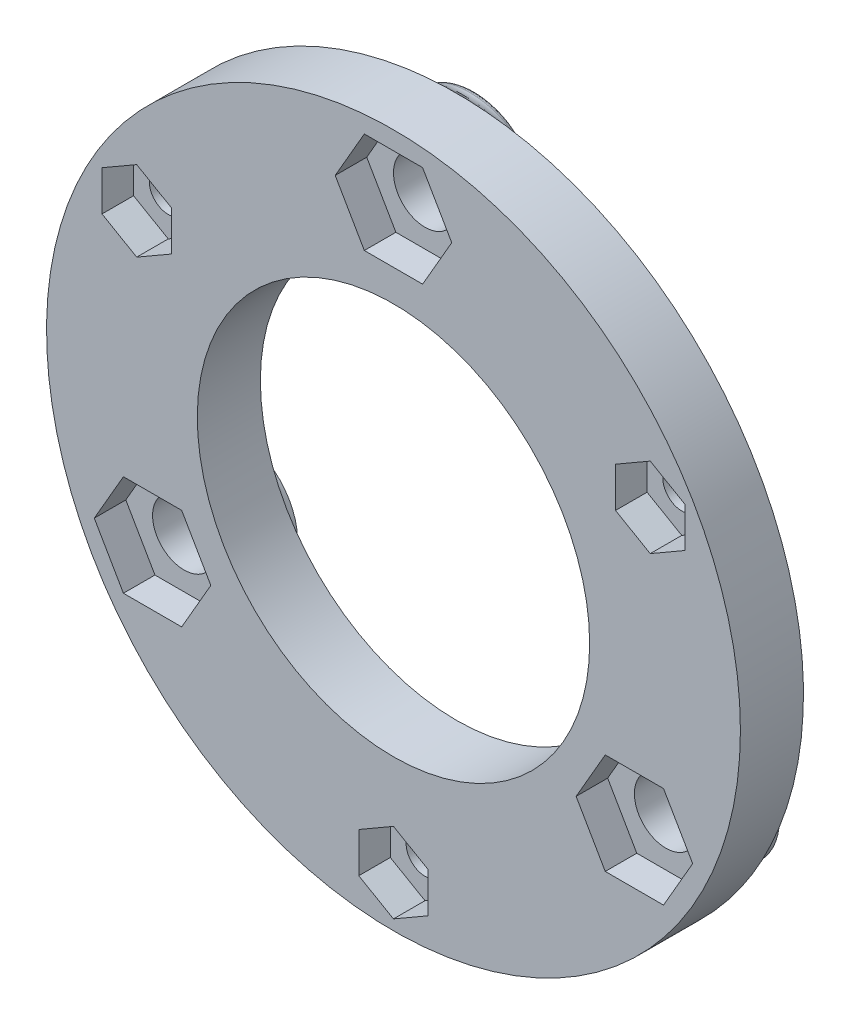
SolidWorks part; units mm, degrees
material "ABS"
ref_plane "Front Plane" through (0, 0, 0) normal (0, 0, 1) x (1, 0, 0)
ref_plane "Top Plane" through (0, 0, 0) normal (0, 1, 0) x (1, 0, 0)
ref_plane "Right Plane" through (0, 0, 0) normal (1, 0, 0) x (0, 0, -1)
sketch "Sketch2" plane through (0, 0, 0) normal (0, 0, 1) x (1, 0, 0)
  line L0 (0, 22.05) -> (0, 0) construction
  line L1 (0, 0) -> (20.3516, 11.75) construction
  circle A0 centre (0, 0) radius 27.5
  circle A1 centre (0, 0) radius 15.55
  circle A2 centre (0, 0) radius 22.05 construction
  circle A3 centre (0, 22.05) radius 2.5
  circle A4 centre (0, 0) radius 23.5 construction
  circle A5 centre (19.0959, -11.025) radius 2.5
  circle A8 centre (20.3516, 11.75) radius 1.5
  circle A9 centre (0, -23.5) radius 1.5
  circle A11 centre (0, 0) radius 6.3 construction
  circle A14 centre (0, 22.05) radius 5 construction
  circle A15 centre (0, 0) radius 17.05 construction
  circle A16 centre (-19.0959, -11.025) radius 2.5
  circle A19 centre (-20.3516, 11.75) radius 1.5
  point P17 (0, 0)
  point P24 (0, 0)
  dimension "D1" = 55
  dimension "D2" = 44.1
  dimension "D4" = 5
  dimension "D7" = 3
  dimension "D3" = 12.6
  dimension "D10" = 10
  dimension "D5" = 4
  dimension "D9" = 1.5
  dimension "D11" = 60
  dimension "D6" = 3
  dimension "D8" = 3
extrude "Boss-Extrude1" add sketch "Sketch2" along normal blind 5
sketch "Sketch3" plane through (0, 0, 5) normal (0, 0, 1) x (1, 0, 0)
  line L0 (0, 22.05) -> (0, 0) construction
  line L13 (-4.6188, 22.05) -> (-2.3094, 18.05)
  line L14 (-2.3094, 18.05) -> (2.3094, 18.05)
  line L15 (2.3094, 18.05) -> (4.6188, 22.05)
  line L16 (4.6188, 22.05) -> (2.3094, 26.05)
  line L17 (2.3094, 26.05) -> (-2.3094, 26.05)
  line L18 (-2.3094, 26.05) -> (-4.6188, 22.05)
  line L20 (20.3516, 8.5746) -> (23.1016, 10.1623)
  line L21 (23.1016, 10.1623) -> (23.1016, 13.3377)
  line L22 (23.1016, 13.3377) -> (20.3516, 14.9254)
  line L23 (20.3516, 14.9254) -> (17.6016, 13.3377)
  line L24 (17.6016, 13.3377) -> (17.6016, 10.1623)
  line L25 (17.6016, 10.1623) -> (20.3516, 8.5746)
  circle A0 centre (0, 22.05) radius 4 construction
  circle A1 centre (20.3516, 11.75) radius 2.75 construction
  dimension "D1" = 8
  dimension "D2" = 5.5
extrude "Cut-Extrude1" cut sketch "Sketch3" against normal blind 2.5
pattern_circular "CirPattern1" count 3 over 360 about axis through (0, 0, 5) along (0, 0, -1) of "Cut-Extrude1" reverse direction yes
sketch "Sketch4" plane through (0, 0, 0) normal (0, 0, -1) x (-1, 0, 0)
  circle A0 centre (0, 22.05) radius 4
  circle A1 centre (0, 22.05) radius 5
  dimension "D1" = 8
extrude "Boss-Extrude2" add sketch "Sketch4" along normal blind 1.5
fillet "Fillet1" radius 1.5 1 edges at (5, 22.05, 0)
fillet "Fillet2" radius 0.5 2 edges at (0, 27.05, -1.5) (0, 17.05, -1.5)
chamfer "Chamfer1" distance 0.25 angle 45 1 edges at (-4, 22.05, -1.5)
pattern_circular "CirPattern2" count 3 over 360 about axis through (0, 0, 5) along (0, 0, -1) of "Fillet1", "Boss-Extrude2", "Chamfer1" reverse direction yes
equation "\"Nr\"= 108"
equation "\"module\"= 0.7"
equation "\"pressure_angle\"= 20.0deg"
equation "\"h_a\"= 0.7"
equation "\"h_f\"= 0.875"
equation "\"clr_tip_root\"= 0.17500000000000004"
equation "\"dp_r\"= 75.6"
equation "\"db_r\"= 71.04076213141467"
equation "\"fw_r\"= 8.0"
equation "\"alpha_r\"= 0.8539582918412449"
equation "\"beta_r\"= 3.374583250349157"
equation "\"bearing_ID\"= 55"
equation "\"bearing_OD\"= 72"
equation "\"bearing_height\"= 9"
equation "\"clearance_planet\"= 1.5"
equation "\"case_dist\"= 6.5"
equation "\"Motor_case_OD_max\"= 111.3"
equation "\"case_mounting_PCD\"= 103.8"
equation "\"bearing mount thickness\"= 8"
equation "\"case_mounting_hole_dia\"= 3"
equation "\"output_mounting_PCD\"= 80"
equation "\"output_mounting_hole_dia\"= 4"
equation "\"clearance_case_mount_holes_shell_thickness\"= 1"
equation "\"motor_case_OD_base\"= 101.8"
equation "\"sec_carrier_thickness\"= 5"
equation "\"sun_coupler_hub_thickness\"= 4"
equation "\"clearance_sun_coupler_sec_carrier\"= 1.5"
equation "\"clearance_motor_and_case\"= 5"
equation "\"motor_OD\"= 86.8"
equation "\"Motor_case_thickness\"= 2.5"
equation "\"Motor_case_ID\"= 96.8"
equation "\"case_mounting_hole_shift\"= 1.0"
equation "\"output_mounting_nut_wrench_size\"= 7"
equation "\"output_mounting_nut_thickness\"= 3.2"
equation "\"case_mounting_hole_allen_socket_dia\"= 5.5"
equation "\"output_mounting_nut_depth\"= 3"
equation "\"case_mounting_bolt_depth\"= 4.5"
equation "\"Ns\"= 18"
equation "\"Np\"= 45"
equation "\"ring_radial_thickness\"= 5.0"
equation "\"ring_OD\"= 85.6"
equation "\"ring_to_chamfer_clearance\"= 2"
equation "\"Motor_case_OD_base_to_chamfer\"= 5"
equation "\"pattern_offset_from_motor_case_OD_base\"= 3"
equation "\"pattern_bulge_dia\"= 3"
equation "\"pattern_num_bulge\"= 18"
equation "\"pattern_depth\"= 2"
equation "\"motor_height\"= 26.5"
equation "\"case_mounting_wrench_size\"= 5.5"
equation "\"case_mounting_nut_clearance\"= 2"
equation "\"base_plate_thickness\"= 4"
equation "\"case_mounting_nut_thickness\"= 2.4"
equation "\"case_mounting_surface_height\"= 4"
equation "\"motor_mount_hole_PCD\"= 32"
equation "\"motor_mount_hole_dia\"= 4"
equation "\"motor_mount_hole_num\"= 4"
equation "\"central_hole_offset_from_motor_mount_PCD\"= 5"
equation "\"wire_slot_dist_from_center\"= 30"
equation "\"wire_slot_length\"= 10"
equation "\"wire_slot_radius\"= 4"
equation "\"driver_upper_holes_dist_from_center\"= 23"
equation "\"driver_lower_holes_dist_from_center\"= 15"
equation "\"driver_side_holes_dist_from_center\"= 20"
equation "\"driver_mount_holes_dia\"= 2.5"
equation "\"driver_mount_inserts_OD\"= 3.5"
equation "\"driver_mount_thickness\"= 1.5"
equation "\"driver_mount_height\"= 4"
equation "\"air_flow_hole_offset\"= 3"
equation "\"num_planet\"= 3"
equation "\"planet_pin_bolt_dia\"= 5"
equation "\"planet_pin_socket_head_dia\"= 8.5"
equation "\"carrier_PCD\"= 44.099999999999994"
equation "\"D1@Sketch2\"=\"bearing_ID\""
equation "\"D2@Sketch2\"=\"carrier_PCD\""
equation "\"D4@Sketch2\"=\"planet_pin_bolt_dia\""
equation "\"D6@Sketch2\"=\"num_planet\""
equation "\"D8@Sketch2\"=\"num_planet\""
equation "\"D1@CirPattern1\"=\"num_planet\""
equation "\"planet_shaft_dia\"= 8"
equation "\"fw_p\"= 8.0"
equation "\"planet_shaft_step_offset\"= 1"
equation "\"carrier_trapezoidal_support_sun_offset\"= 5"
equation "\"carrier_trapezoidal_support_hole_PCD_offset_bearing_ID\"= 4"
equation "\"carrier_trapezoidal_support_hole_dia\"= 3"
equation "\"carrier_trapezoidal_support_hole_socket_head_dia\"= 5.5"
equation "\"carrier_bearing_step_width\"= 1.5"
equation "\"standard_clearance_1_5mm\"= 1.5"
equation "\"standard_fillet_1_5mm\"= 1.5"
equation "\"sun_shaft_bearing_OD\"= 16"
equation "\"sun_shaft_bearing_width\"= 5"
equation "\"standard_bearing_insertion_chamfer\"= 0.5"
equation "\"D7@Sketch2\"=\"carrier_trapezoidal_support_hole_dia\""
equation "\"D5@Sketch2\"=\"carrier_trapezoidal_support_hole_PCD_offset_bearing_ID\""
equation "\"D3@Sketch2\"=\"Ns\"*\"module\""
equation "\"carrier_trapezoidal_support_hole_wrench_size\"= 5.5"
equation "\"planet_pin_bolt_wrench_size\"= 8"
equation "\"D1@Boss-Extrude1\"=\"sec_carrier_thickness\""
equation "\"D1@Cut-Extrude1\"=\"sec_carrier_thickness\"/2"
equation "\"D1@Sketch4\"=\"planet_shaft_dia\""
equation "\"D2@Sketch4\"=\"planet_shaft_step_offset\""
equation "\"D1@Boss-Extrude2\"=\"clearance_planet\""
equation "\"D1@Fillet1\"=\"standard_fillet_1_5mm\""
equation "\"D1@Chamfer1\"=\"standard_bearing_insertion_chamfer\"/2"
equation "\"D1@Fillet2\"=\"standard_fillet_1_5mm\"/3"
equation "\"D1@CirPattern2\"=\"num_planet\""
equation "\"D10@Sketch2\"=\"planet_shaft_dia\"+\"planet_shaft_step_offset\"*2"
equation "\"D9@Sketch2\"=\"standard_clearance_1_5mm\""
equation "\"D1@Sketch3\"=\"planet_pin_bolt_wrench_size\""
equation "\"D11@Sketch2\"=180/\"num_planet\""
equation "\"D2@Sketch3\"=\"carrier_trapezoidal_support_hole_wrench_size\""
equation "\"pressure angle\"= 20.0deg"
equation "\"motor_output_hole_PCD\"= 23"
equation "\"motor_output_hole_dia\"= 4"
equation "\"motor_output_hole_num\"= 4"
equation "\"h_b\"= 0.875"
equation "\"dp_s\"= 12.6"
equation "\"db_s\"= 11.840127021902445"
equation "\"fw_s_calc\"= 6.9645987548691926"
equation "\"alpha_s\"= 0.8539582918412556"
equation "\"beta_s\"= 8.292083416317489"
equation "\"dp_p\"= 31.499999999999996"
equation "\"db_p\"= 29.600317554756113"
equation "\"alpha_p\"= 0.8539582918412343"
equation "\"beta_p\"= 2.2920834163175314"
equation "\"planet_bearing_OD\"= 12"
equation "\"planet_bearing_width\"= 3.5"
equation "\"planet_bore\"= 10"
equation "\"sun_shaft_bearing_ID\"= 8"
equation "\"sun_hub_dia\"= 33.0"
equation "\"sun_central_bolt_dia\"= 5"
equation "\"sun_central_bolt_socket_head_dia\"= 8.5"
equation "\"fw_s_used\"= 16.0"
equation "\"motor_output_hole_CSK_OD\"= 8"
equation "\"motor_output_hole_CSK_head_height\"= 2.0"
equation "\"bearing_retainer_thickness\"= 2"
